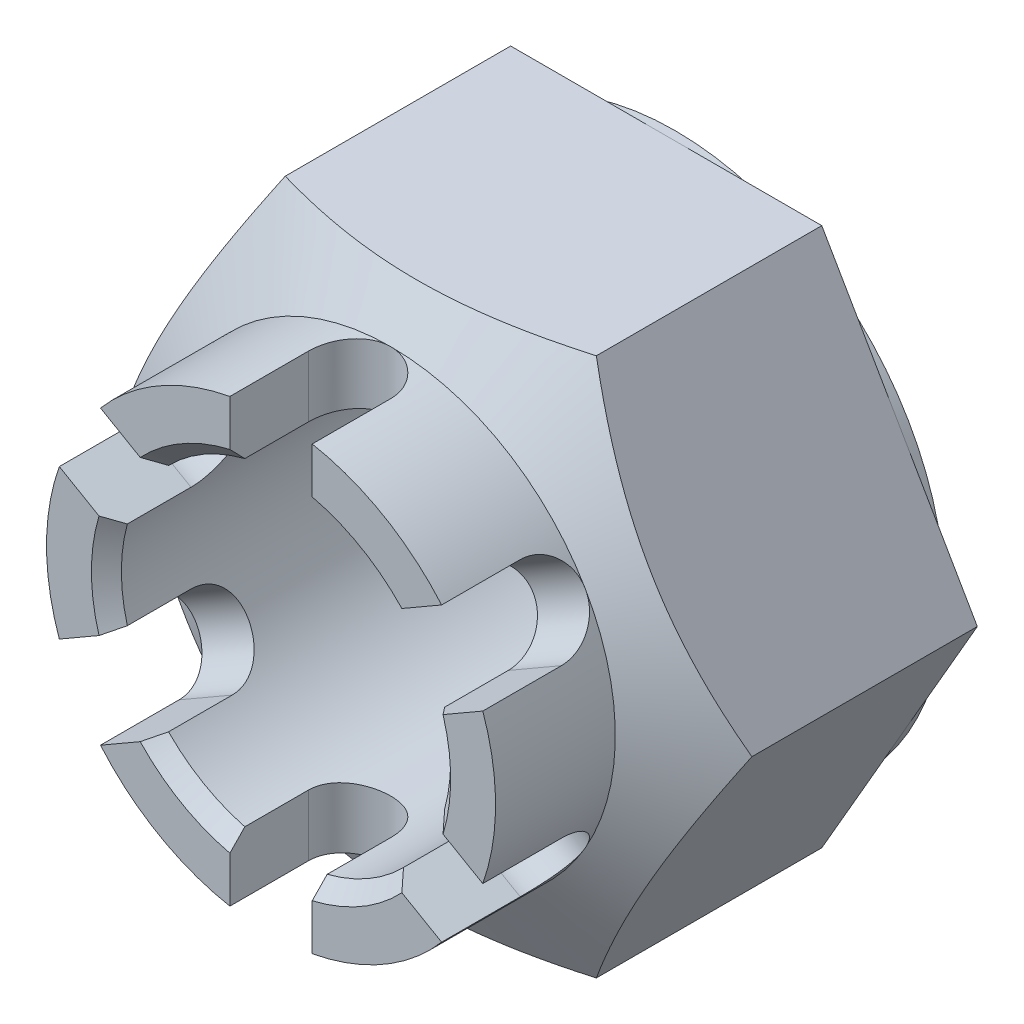
SolidWorks part; units mm, degrees
material "AISI 1020"
ref_plane "Front" through (0, 0, 0) normal (0, 0, 1) x (1, 0, 0)
ref_plane "Top" through (0, 0, 0) normal (0, 1, 0) x (1, 0, 0)
ref_plane "Right" through (0, 0, 0) normal (1, 0, 0) x (0, 0, -1)
ref_axis "Axis1" through (-84.4107, 0, 0) along (1, 0, 0)
ref_axis "Axis2" through (0, 64.3378, 0) along (0, -1, 0)
ref_axis "Axis3" through (0, 0, -102.329) along (0, 0, 1)
sketch "Sketch1" plane through (0, 0, 0) normal (0, 0, 1) x (1, 0, 0)
  line L1 (20.7846, 0) -> (10.3923, 18)
  line L2 (10.3923, 18) -> (-10.3923, 18)
  line L3 (-10.3923, 18) -> (-20.7846, 0)
  line L4 (-20.7846, 0) -> (-10.3923, -18)
  line L5 (-10.3923, -18) -> (10.3923, -18)
  line L6 (10.3923, -18) -> (20.7846, 0)
  circle A0 centre (0, 0) radius 18 construction
  dimension "D1" = 36
extrude "Boss-Extrude1" add sketch "Sketch1" along normal blind 19
sketch "Sketch2" plane through (0, 0, 19) normal (0, 0, 1) x (1, 0, 0)
  circle A0 centre (0, 0) radius 15
  dimension "D1" = 30
extrude "Boss-Extrude2" add sketch "Sketch2" along normal blind 8
sketch "Sketch3" plane through (0, 0, 0) normal (1, 0, 0) x (0, 0, -1)
  line L4 (-19, 15) -> (-19, 25.9778)
  line L5 (-19, 25.9778) -> (-12.662, 25.9778)
  line L6 (-12.662, 25.9778) -> (-19, 15)
  dimension "D1" = 30
revolve "Cut-Revolve1" cut sketch "Sketch3" angle 360 about axis through (0, 0, -102.329) along (0, 0, 1)
sketch "Sketch4" plane through (0, 0, 0) normal (0, 0, -1) x (-1, 0, 0)
  circle A0 centre (0, 0) radius 18
extrude "Cut-Extrude-Thin1" cut sketch "Sketch4" against normal blind 0.6 thin thin type one direction wall 10
sketch "Sketch5" plane through (0, 0, 27) normal (0, 0, 1) x (1, 0, 0)
  circle A0 centre (0, 0) radius 11
  dimension "D1" = 22
extrude "Cut-Extrude1" cut sketch "Sketch5" against normal up to next
sketch "Sketch6" plane through (0, 0, 0) normal (0, 1, 0) x (1, 0, 0)
  line L0 (0, -27) -> (0, -19) construction
  line L1 (-15, -27) -> (15, -27) construction
  line L2 (-15, -19) -> (15, -19) construction
  line L3 (-2.75, -21.75) -> (-2.75, -27)
  line L4 (-2.75, -27) -> (2.75, -27)
  line L5 (2.75, -27) -> (2.75, -21.75)
  arc A0 (2.75, -21.75) -> (-2.75, -21.75) centre (0, -21.75) ccw
  dimension "D1" = 5.5
  dimension "D2" = 2.75
extrude "Cut-Extrude2" cut sketch "Sketch6" against normal up to next
pattern_circular "CirPattern1" count 6 over 360 about axis through (0, 0, -0.001) along (0, 0, 1) of "Cut-Extrude2" reverse direction yes
ref_axis "Axis4" through (15.0203, 8.672, 21.75) along (-0.866, -0.5, 0)
chamfer "Chamfer1" distance 1 angle 45 7 edges at (-5.5, -9.5263, 27) (-11, 0, 27) (-5.5, 9.5263, 27) (5.5, 9.5263, 27) (11, 0, 27) (5.5, -9.5263, 27) (11, 0, 0)
